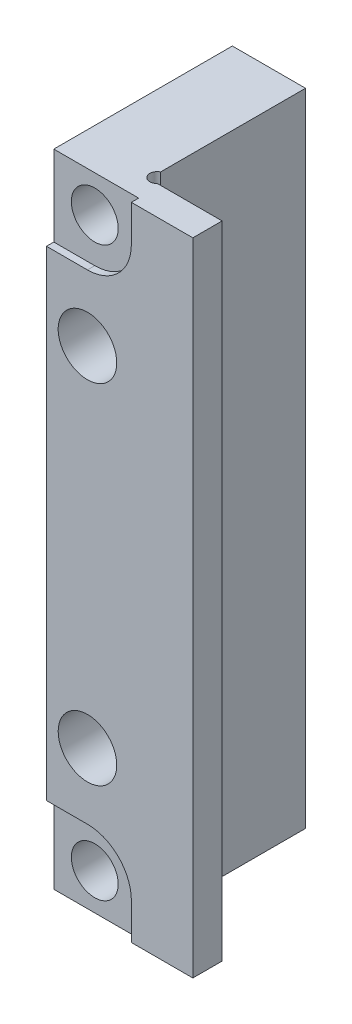
SolidWorks part; units mm, degrees
ref_plane "前基準面" through (0, 0, 0) normal (0, 0, 1) x (1, 0, 0)
ref_plane "上基準面" through (0, 0, 0) normal (0, 1, 0) x (1, 0, 0)
ref_plane "右基準面" through (0, 0, 0) normal (1, 0, 0) x (0, 0, -1)
sketch "草圖1" plane through (0, 0, 0) normal (0, 0, 1) x (1, 0, 0)
  line L0 (-29.9, 26.9) -> (-29.9, -26.9) construction
  line L1 (-38, 30) -> (38, 30) construction
  line L2 (-38, 30) -> (-38, -30) construction
  line L3 (-38, -30) -> (38, -30) construction
  line L4 (38, 30) -> (38, -30) construction
  line L5 (-38, 30) -> (38, -30) construction
  line L6 (-38, -30) -> (38, 30) construction
  line L7 (-29.9, 26.9) -> (29.9, 26.9) construction
  line L8 (-34.9, 21.9) -> (-34.9, -21.9) construction
  line L9 (-29.9, -26.9) -> (29.9, -26.9) construction
  line L10 (34.9, 21.9) -> (34.9, -21.9) construction
  line L11 (-34.9, 26.9) -> (34.9, -26.9) construction
  line L12 (-34.9, -26.9) -> (34.9, 26.9) construction
  line L13 (-34.9, 21.9) -> (-24.9, 21.9)
  line L14 (-24.9, 21.9) -> (-24.9, -21.9)
  line L15 (-24.9, -21.9) -> (-34.9, -21.9)
  line L16 (-34.9, 21.9) -> (-34.9, -21.9)
  arc A0 (29.9, -26.9) -> (34.9, -21.9) centre (29.9, -21.9) ccw construction
  arc A1 (29.9, 26.9) -> (34.9, 21.9) centre (29.9, 21.9) cw construction
  arc A2 (-34.9, -21.9) -> (-29.9, -26.9) centre (-29.9, -21.9) ccw construction
  arc A3 (-29.9, 26.9) -> (-34.9, 21.9) centre (-29.9, 21.9) ccw construction
  point P0 (0, 0)
  point P6 (0, 0)
  dimension "D5" = 5
  dimension "D1" = 76
  dimension "D2" = 60
  dimension "D3" = 3.1
  dimension "D4" = 3.1
  dimension "D6" = 5
  dimension "D7" = 10
extrude "填料-伸長1" add sketch "草圖1" against normal blind 10
sketch "草圖2" plane through (0, -21.9, 0) normal (0, -1, 0) x (1, 0, 0)
  line L0 (-24.9, -10) -> (-24.9, -2)
  line L1 (-24.9, -10) -> (-24.9, 0) construction
  line L2 (-24.9, -2) -> (-29.9, -2)
  line L3 (-29.9, -2) -> (-29.9, -10)
  line L4 (-34.9, -10) -> (-24.9, -10) construction
  line L5 (-29.9, -10) -> (-24.9, -10)
  line L6 (-27.4, -2) -> (-27.4, -10) construction
  line L7 (-29.9, -6) -> (-24.9, -6) construction
  line L8 (-27.4, -6) -> (-29.9, -2) construction
  circle A0 centre (-29.684, -2.3456) radius 0.5
  line M6 (-24.9, -10) -> (-24.9, 0)
  dimension "D3" = 1
  dimension "D4" = 0.3456
  dimension "D1" = 8
  dimension "D2" = 5
extrude "除料-伸長1" cut sketch "草圖2" against normal through all contours L3 A0 L2 | L3 L5 L2 A0 M6 | A0 region at (-27.3706, -21.9, -6.0487) region at (-29.5737, -21.9, -2.3984)
sketch "草圖3" plane through (0, 0, 0) normal (0, 0, 1) x (1, 0, 0)
  line L0 (-34.9, 21.9) -> (-34.9, -21.9) construction
  line L1 (-24.9, 21.9) -> (-34.9, 21.9) construction
  line L2 (0, 0) -> (-34.9, 0) construction
  circle A0 centre (-32.1, 19.4) radius 1.6
  circle A1 centre (-32.1, -19.4) radius 1.6
  dimension "D1" = 3.2
  dimension "D2" = 2.8
  dimension "D3" = 2.5
extrude "除料-伸長2" cut sketch "草圖3" against normal through all
sketch "草圖4" plane through (0, 0, 0) normal (0, 0, 1) x (1, 0, 0)
  line L0 (-34.9, 21.9) -> (-34.9, -21.9) construction
  line L1 (-24.9, 21.9) -> (-34.9, 21.9) construction
  line L2 (-34.9, 0) -> (-24.9, 0) construction
  line L3 (-24.9, -21.9) -> (-24.9, 21.9) construction
  circle A0 centre (-32.1, 11.9) radius 2
  circle A1 centre (-32.1, -11.9) radius 2
  circle A2 centre (-32.1, 19.4) radius 1.6 construction
  dimension "D1" = 2.8
  dimension "D3" = 4
  dimension "D4" = 11.9
  dimension "D5" = 2.8
  dimension "D2" = 10
  dimension "D6" = 7.5
extrude "除料-伸長3" cut sketch "草圖4" against normal through all
sketch "草圖5" plane through (0, 0, 0) normal (0, 0, 1) x (1, 0, 0)
  line L0 (-29.1, 19.4) -> (-29.1, 21.9)
  line L1 (-24.9, 21.9) -> (-34.9, 21.9) construction
  line L2 (-29.1, 21.9) -> (-34.9, 21.9)
  line L3 (-32.1, 16.4) -> (-34.9, 16.4)
  line L4 (-34.9, 21.9) -> (-34.9, -21.9) construction
  line L5 (-34.9, 16.4) -> (-34.9, 21.9)
  line L6 (-29.1, -19.4) -> (-29.1, -21.9)
  line L9 (-32.1, -16.4) -> (-34.9, -16.4)
  line L10 (-34.9, -16.4) -> (-34.9, -21.9)
  line L13 (-29.1, -21.9) -> (-34.9, -21.9)
  circle A1 centre (-32.1, -19.4) radius 3 construction
  arc A2 (-29.1, 19.4) -> (-32.1, 16.4) centre (-32.1, 19.4) cw
  arc A3 (-32.1, -16.4) -> (-29.1, -19.4) centre (-32.1, -19.4) cw
  circle A5 centre (-32.1, 19.4) radius 3 construction
  dimension "D1" = 6
  dimension "D2" = 6
  dimension "D3" = 2.5
  dimension "D4" = 2.8
extrude "除料-伸長4" cut sketch "草圖5" against normal blind 0.5
sketch "草圖6" plane through (0, 0, -10) normal (0, 0, -1) x (-1, 0, 0)
  line L4 (29.9, 21.9) -> (29.9, -21.9)
  line L5 (29.9, -21.9) -> (34.9, -21.9)
  line L6 (34.9, -21.9) -> (34.9, 21.9)
  line L7 (34.9, 21.9) -> (29.9, 21.9)
  line L8 (29.9, 21.9) -> (29.9, -21.9)
  line L9 (29.9, -21.9) -> (34.9, -21.9)
  line L10 (34.9, -21.9) -> (34.9, 21.9)
  line L11 (34.9, 21.9) -> (29.9, 21.9)
  circle A0 centre (32.1, 19.4) radius 1.6 construction
  circle A1 centre (32.1, 19.4) radius 1.6
  circle A2 centre (32.1, 11.9) radius 2 construction
  circle A3 centre (32.1, 11.9) radius 2
  circle A4 centre (32.1, -11.9) radius 2 construction
  circle A5 centre (32.1, -11.9) radius 2
  circle A6 centre (32.1, -19.4) radius 1.6 construction
  circle A7 centre (32.1, -19.4) radius 1.6
  dimension "D1" = 0
extrude "填料-伸長2" add sketch "草圖6" along normal blind 2.7
